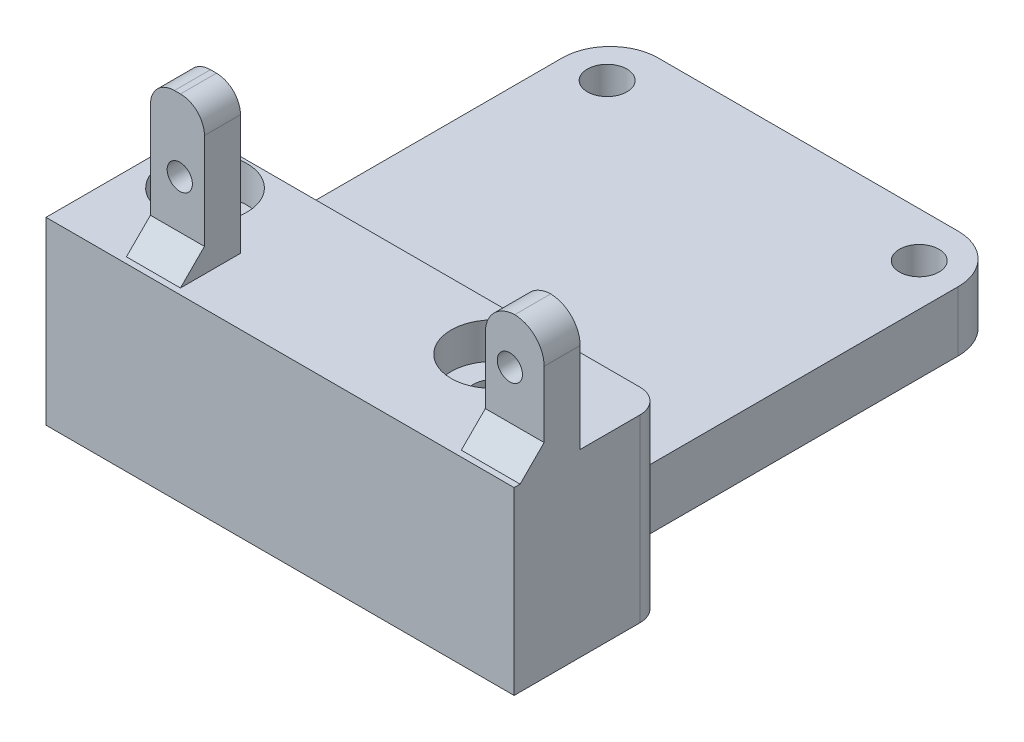
SolidWorks part; units mm, degrees
ref_plane "Front Plane" through (0, 0, 0) normal (0, 0, 1) x (1, 0, 0)
ref_plane "Top Plane" through (0, 0, 0) normal (0, 1, 0) x (1, 0, 0)
ref_plane "Right Plane" through (0, 0, 0) normal (1, 0, 0) x (0, 0, -1)
sketch "Sketch1" plane through (0, 0, 0) normal (0, 1, 0) x (1, 0, 0)
  line L1 (0, 0) -> (33, 0)
  line L2 (0, 0) -> (0, 42)
  line L3 (0, 42) -> (33, 42)
  line L4 (33, 0) -> (33, 42)
  dimension "D1" = 42
  dimension "D2" = 33
extrude "Boss-Extrude1" add sketch "Sketch1" along normal blind 5
ref_plane "Plane1" through (23, 0, -42) normal (1, 0, 0) x (0, 0, -1)
sketch "Sketch4" plane through (0, 5, 0) normal (0, 1, 0) x (1, 0, 0)
  circle A0 centre (4.5, 3.75) radius 1.65 construction
  circle A1 centre (3.5, 38.25) radius 1.65 construction
  circle A2 centre (29.5, 38.25) radius 1.65 construction
  circle A3 centre (28.5, 3.75) radius 1.65 construction
  circle A4 centre (4.5, 3.75) radius 1.65
  circle A5 centre (3.5, 38.25) radius 1.65
  circle A6 centre (29.5, 38.25) radius 1.65
  circle A7 centre (28.5, 3.75) radius 1.65
extrude "Cut-Extrude1" cut sketch "Sketch4" against normal blind 10
sketch "Sketch6" plane through (0, 5, 0) normal (0, 1, 0) x (1, 0, 0)
  line L0 (33, 0) -> (33, 42) construction
  line L1 (33, 0) -> (39, 0)
  line L2 (33, 0) -> (33, 7.4907)
  line L3 (33, 7.4907) -> (39, 7.4907)
  line L4 (39, 0) -> (39, 7.4907)
  line L5 (39, -5) -> (0, -5)
  line L6 (39, -5) -> (39, 0)
  line L7 (39, 0) -> (0, 0)
  line L8 (0, -5) -> (0, 0)
  line M11 (0, 0) -> (33, 0)
  line M12 (33, 0) -> (33, 42)
  dimension "D1" = 5
  dimension "D2" = 6
extrude "Boss-Extrude2" add sketch "Sketch6" against normal blind 5 contours L1 L4 L3 M12 | L8 L5 L6 L1 M11 region at (36, 5, -3.7453) region at (19.5, 5, 2.5)
sketch "Sketch8" plane through (0, 5, 0) normal (0, 1, 0) x (1, 0, 0)
  line L6 (39, 7.4907) -> (33, 7.4907)
  line L7 (33, 7.4907) -> (33, 42)
  line L8 (33, 42) -> (0, 42)
  line L9 (0, 42) -> (0, -5)
  line L10 (0, -5) -> (39, -5)
  line L11 (39, -5) -> (39, 7.4907)
  line L12 (39, 7.4907) -> (33, 7.4907)
  line L13 (33, 7.4907) -> (33, 42)
  line L14 (33, 42) -> (0, 42)
  line L15 (0, 42) -> (0, -5)
  line L16 (0, -5) -> (39, -5)
  line L17 (39, -5) -> (39, 7.4907)
  circle A0 centre (29.5, 38.25) radius 1.65 construction
  circle A1 centre (3.5, 38.25) radius 1.65 construction
  circle A2 centre (4.5, 3.75) radius 1.65 construction
  circle A3 centre (28.5, 3.75) radius 1.65 construction
  circle A4 centre (29.5, 38.25) radius 1.65
  circle A5 centre (3.5, 38.25) radius 1.65
  circle A6 centre (4.5, 3.75) radius 1.65
  circle A7 centre (28.5, 3.75) radius 1.65
  dimension "D1" = 0
extrude "Boss-Extrude4" add sketch "Sketch8" along normal blind 10
sketch "Sketch9" plane through (0, 15, 0) normal (0, 1, 0) x (1, 0, 0)
  line L0 (39, -5) -> (39, 7.4907) construction
  line L1 (39, 0.5) -> (34.1, 0.5)
  line L2 (39, 0.5) -> (39, -2.5)
  line L3 (39, -2.5) -> (34.1, -2.5)
  line L4 (34.1, 0.5) -> (34.1, -2.5)
  line L5 (0, -5) -> (39, -5) construction
  dimension "D1" = 3
  dimension "D2" = 2.5
  dimension "D3" = 4.9
extrude "Boss-Extrude5" add sketch "Sketch9" along normal blind 10
fillet "Fillet2" radius 2.5 2 edges at (34.1, 25, 1) (39, 25, 1)
sketch "Sketch10" plane through (0, 0, -0.5) normal (0, 0, -1) x (-1, 0, 0)
  arc A0 (-37.0682, 20.5) -> (-37.0682, 21.5) centre (-36.1449, 21) ccw construction
  arc A1 (-37.0682, 20.5) -> (-37.0682, 21.5) centre (-36.1449, 21) ccw
  circle A2 centre (-36.1449, 21) radius 1.05
extrude "Cut-Extrude3" cut sketch "Sketch10" against normal blind 10 contours A1 A2 region at (36.1449, 21, -0.5)
sketch "Sketch11" plane through (0, 15, 0) normal (0, 1, 0) x (1, 0, 0)
  line L1 (0, 42) -> (33, 42)
  line L2 (0, 42) -> (0, 7.4907)
  line L3 (0, 7.4907) -> (33, 7.4907)
  line L4 (33, 42) -> (33, 7.4907)
extrude "Cut-Extrude4" cut sketch "Sketch11" against normal blind 10
fillet "Fillet3" radius 4 3 edges at (33, 2.5, -7.4907) (0, 2.5, -42) (33, 2.5, -42)
fillet "Fillet4" radius 2 1 edges at (39, 7.5, -7.4907)
fillet "Fillet5" radius 4 1 edges at (18.5, 5, -7.4907)
sketch "Sketch12" plane through (0, 15, 0) normal (0, 1, 0) x (1, 0, 0)
  circle A0 centre (4.5, 3.75) radius 3.5
  circle A1 centre (28.5, 3.75) radius 3.5
  dimension "D1" = 7
  dimension "D2" = 7
extrude "Cut-Extrude5" cut sketch "Sketch12" against normal blind 3
sketch "Sketch13" plane through (0, 15, 0) normal (0, 1, 0) x (1, 0, 0)
  line L0 (0, 7.4907) -> (0, -5) construction
  line L1 (10.7, 0.5) -> (6.2, 0.5)
  line L2 (10.7, 0.5) -> (10.7, -2.5)
  line L3 (10.7, -2.5) -> (6.2, -2.5)
  line L4 (6.2, 0.5) -> (6.2, -2.5)
  line L5 (6.3699, 0.5) -> (11.1449, 0.5) construction
  dimension "D1" = 4.5
  dimension "D2" = 6.2
  dimension "D3" = 3
  dimension "D4" = 0
extrude "Boss-Extrude6" add sketch "Sketch13" along normal up to surface (12 mm away)
fillet "Fillet6" radius 2 2 edges at (6.2, 27, 1) (10.7, 27, 1)
sketch "Sketch14" plane through (0, 0, -0.5) normal (0, 0, -1) x (-1, 0, 0)
  arc A0 (-7.7216, 21.5) -> (-7.7216, 20.5) centre (-8.6449, 21) ccw construction
  arc A1 (-7.7216, 21.5) -> (-7.7216, 20.5) centre (-8.6449, 21) ccw
  circle A2 centre (-8.6449, 21) radius 1.05
extrude "Cut-Extrude6" cut sketch "Sketch14" against normal blind 7 contours A1 A2 region at (8.6449, 21, -0.5)
chamfer "Chamfer1" distance 2 angle 45 2 edges at (36.55, 15, 2.5) (8.45, 15, 2.5)
